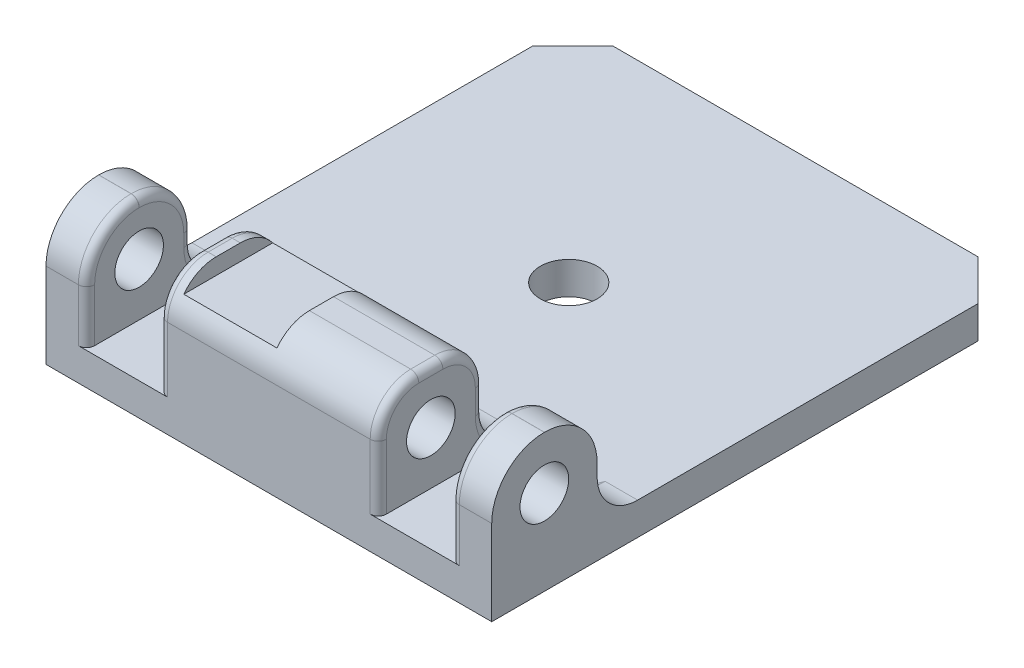
SolidWorks part; units mm, degrees
ref_plane "Alzado" through (0, 0, 0) normal (0, 0, 1) x (1, 0, 0)
ref_plane "Planta" through (0, 0, 0) normal (0, 1, 0) x (1, 0, 0)
ref_plane "Vista lateral" through (0, 0, 0) normal (1, 0, 0) x (0, 0, -1)
sketch "Croquis1" plane through (0, 0, 0) normal (0, 1, 0) x (1, 0, 0)
  line L1 (-27.5, -32.5) -> (27.5, -32.5)
  line L2 (-27.5, -32.5) -> (-27.5, 32.5)
  line L3 (-27.5, 32.5) -> (27.5, 32.5)
  line L4 (27.5, -32.5) -> (27.5, 32.5)
  line L5 (-27.5, -32.5) -> (27.5, 32.5) construction
  line L6 (-27.5, 32.5) -> (27.5, -32.5) construction
  point P0 (0, 0)
  dimension "D1" = 55
  dimension "D2" = 65
extrude "Saliente-Extruir1" add sketch "Croquis1" along normal blind 4
sketch "Croquis5" plane through (0, 0, 0) normal (0, -1, 0) x (1, 0, 0)
  line L0 (0, -32.5) -> (0, -4.5) construction
  line L1 (27.5, -32.5) -> (-27.5, -32.5) construction
  line L2 (-27.5, 32.5) -> (27.5, 32.5) construction
  circle A0 centre (0, -4.5) radius 3.5
  dimension "D2" = 7
  dimension "D3" = 37
  dimension "D1" = 28
extrude "Cortar-Extruir5" cut sketch "Croquis5" against normal blind 72
chamfer "Chaflán1" distance 5 angle 45 2 edges at (-27.5, 2, -32.5) (27.5, 2, -32.5)
sketch "Croquis6" plane through (-27.5, 0, 0) normal (-1, 0, 0) x (0, 0, 1)
  line L1 (32.5, 0) -> (19.5, 0)
  line L2 (32.5, 0) -> (32.5, 10.51)
  line L3 (26.01, 17) -> (25.99, 17)
  line L4 (19.5, 0) -> (19.5, 10.51)
  arc A0 (32.5, 10.51) -> (26.01, 17) centre (26.01, 10.51) ccw
  arc A1 (25.99, 17) -> (19.5, 10.51) centre (25.99, 10.51) ccw
  circle A2 centre (26.01, 10.51) radius 3
  point P7 (32.5, 17)
  point P10 (19.5, 17)
  dimension "D3" = 6.49
  dimension "D4" = 6
  dimension "D1" = 17
  dimension "D2" = 13
extrude "Saliente-Extruir2" add sketch "Croquis6" against normal up to surface (55 mm away) up to face at (27.5, 2, 2.5)
fillet "Redondeo1" radius 5 1 edges at (0, 4, 19.5)
sketch "Croquis7" plane through (0, 4, 0) normal (0, 1, 0) x (1, 0, 0)
  line L0 (0, 4.5) -> (0, -32.5) construction
  line L1 (27.5, -32.5) -> (-27.5, -32.5) construction
  line L2 (0, -32.5) -> (-22.5, -32.5) construction
  line L3 (27.5, -19.5) -> (-27.5, -19.5) construction
  line L4 (-22.5, -32.5) -> (22.5, -32.5)
  line L5 (-22.5, -32.5) -> (-22.5, -19.5)
  line L6 (-22.5, -19.5) -> (22.5, -19.5)
  line L7 (22.5, -32.5) -> (22.5, -19.5)
  line L9 (-22.5, -19.5) -> (22.5, -19.5)
  line L10 (-22.5, -19.5) -> (-22.5, -11.9743)
  line L11 (-22.5, -11.9743) -> (22.5, -11.9743)
  line L12 (22.5, -19.5) -> (22.5, -11.9743)
  dimension "D1" = 45
extrude "Cortar-Extruir7" cut sketch "Croquis7" along normal blind 20 contours L5 L4 L7 L6 | L10 L9 L12 L11
fillet "Redondeo2" radius 1 12 edges at (22.5, 5.4645, 18.0355) (22.5, 9.755, 19.5) (22.5, 7.255, 32.5) (22.5, 17, 26) (-22.5, 5.4645, 18.0355) (-22.5, 9.755, 19.5) (-22.5, 7.255, 32.5) (-22.5, 17, 26) (22.5, 15.0991, 30.5991) (22.5, 15.0991, 21.4009) (-22.5, 15.0991, 30.5991) (-22.5, 15.0991, 21.4009)
sketch "Croquis8" plane through (0, 4, 0) normal (0, 1, 0) x (1, 0, 0)
  line L0 (-13.5, -32.5253) -> (13.5, -32.5)
  line L1 (-23.5, -32.5) -> (23.5, -32.5) construction
  line L2 (0, 0) -> (0, -32.5126) construction
  line L4 (-13.5, -32.5253) -> (13.5, -32.5253)
  line L5 (-13.5, -32.5253) -> (-13.5, -19.5253)
  line L6 (-13.5, -19.5253) -> (13.5, -19.5253)
  line L7 (13.5, -32.5253) -> (13.5, -19.5253)
  point P5 (0, -32.5126)
  line M9 (-23.5, -32.5) -> (23.5, -32.5)
  dimension "D1" = 27
  dimension "D2" = 13
extrude "Saliente-Extruir3" add sketch "Croquis8" along normal blind 13 contours L2 L6 L5 M9 | L6 L2 L7 M9 region at (-6.75, 4, 26.0126) region at (6.75, 4, 26.0126)
fillet "Redondeo3" radius 5 2 edges at (0, 17, 19.5253) (0, 17, 32.5)
fillet "Redondeo4" radius 5 1 edges at (0, 4, 19.5253)
fillet "Redondeo5" radius 1 12 edges at (13.5, 5.4645, 18.0608) (13.5, 10.5, 19.5253) (13.5, 8, 32.5) (-13.5, 5.4645, 18.0608) (-13.5, 10.5, 19.5253) (-13.5, 8, 32.5) (13.5, 15.5355, 20.9897) (13.5, 15.5355, 31.0355) (-13.5, 15.5355, 20.9897) (-13.5, 15.5355, 31.0355) (13.5, 17, 26.0126) (-13.5, 17, 26.0126)
sketch "Croquis10" plane through (-13.5, 0, 0) normal (-1, 0, 0) x (0, 0, 1)
  circle A0 centre (26.01, 10.51) radius 3
extrude "Cortar-Extruir8" cut sketch "Croquis10" against normal up to surface (27 mm away) up to face at (13.5, 10.6171, 24.9352)
sketch "Croquis11" plane through (0, 17, 0) normal (0, 1, 0) x (1, 0, 0)
  line L0 (-12.5, -26.0126) -> (-11.5, -26.0126) construction
  line L1 (-12.5, -24.5253) -> (-12.5, -27.5) construction
  line L2 (-11.5, -26.0126) -> (0, -26.0126) construction
  line L4 (-11.5, -32.9473) -> (0, -32.9473)
  line L5 (-11.5, -32.9473) -> (-11.5, -19.078)
  line L6 (-11.5, -19.078) -> (0, -19.078)
  line L7 (0, -32.9473) -> (0, -19.078)
  line L8 (-11.5, -32.9473) -> (0, -19.078) construction
  line L9 (-11.5, -19.078) -> (0, -32.9473) construction
  line L10 (-11.5, -19.078) -> (-14.1134, -19.078)
  line L11 (-11.5, -19.078) -> (-11.5, -32.9473)
  line L12 (-11.5, -32.9473) -> (-14.1134, -32.9473)
  line L13 (-14.1134, -19.078) -> (-14.1134, -32.9473)
  point P4 (-5.75, -26.0126)
  line M3 (-12.5, -27.5) -> (12.5, -27.5)
  line M5 (12.5, -24.5253) -> (-12.5, -24.5253)
  dimension "D1" = 1
  dimension "D2" = 11.5
extrude "Cortar-Extruir9" cut sketch "Croquis11" against normal blind 2 contours L7 L6 L5 M5 | L7 L5 M3 M5 | L4 L7 L5 M3 region at (-5.75, 17, 30.2236) region at (-5.75, 17, 26.0126) region at (-5.75, 17, 21.8016)
